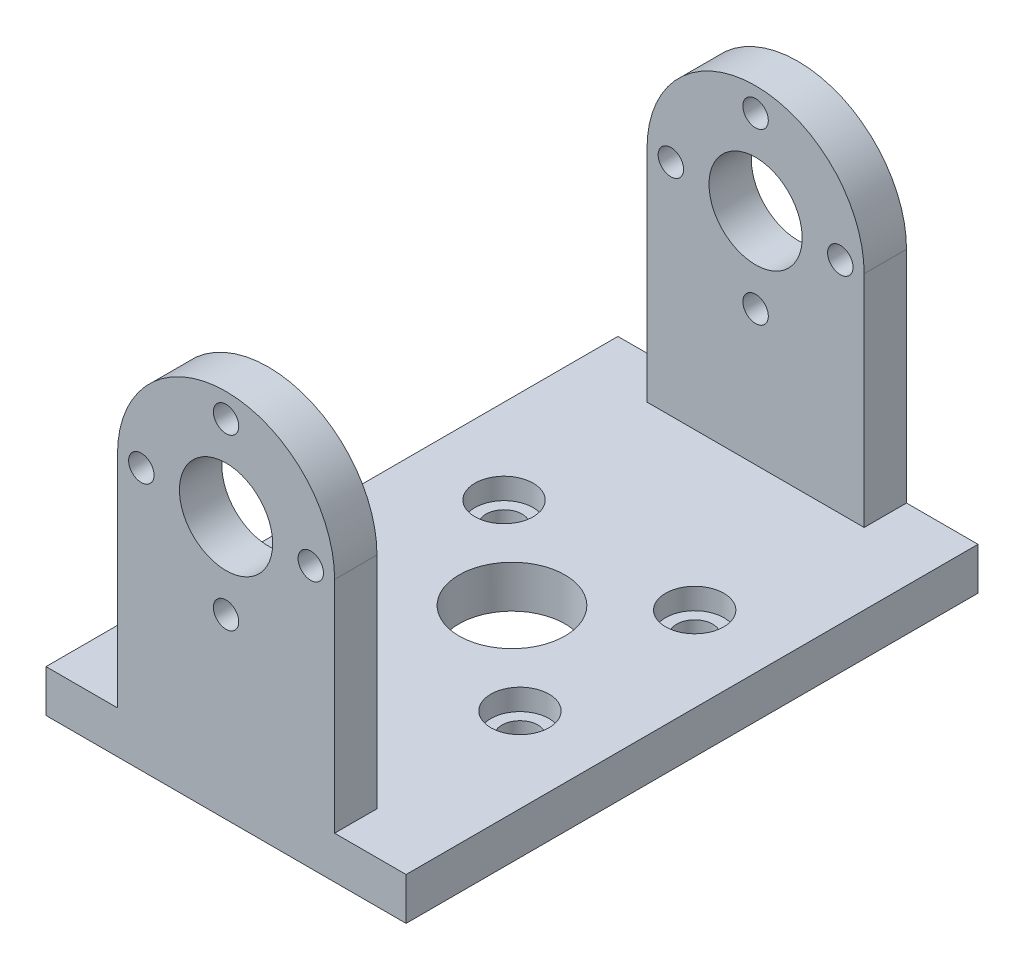
SolidWorks part; units mm, degrees
ref_plane "Front Plane" through (0, 0, 0) normal (0, 0, 1) x (1, 0, 0)
ref_plane "Top Plane" through (0, 0, 0) normal (0, 1, 0) x (1, 0, 0)
ref_plane "Right Plane" through (0, 0, 0) normal (1, 0, 0) x (0, 0, -1)
sketch "Sketch1" plane through (0, 0, 0) normal (0, 0, 1) x (1, 0, 0)
  line L0 (0, 0) -> (0, -68) construction
  line L1 (10.25, 0) -> (10.25, -68)
  line L2 (-10.25, 0) -> (-10.25, -68)
  line L3 (0, 0) -> (0, -68) construction
  line L4 (17, 0) -> (17, -68)
  line L5 (-17, 0) -> (-17, -68)
  line L7 (-10.25, -68) -> (10.25, -68)
  line L8 (-10.25, -68) -> (-10.25, -32.75)
  line L9 (-10.25, -32.75) -> (10.25, -32.75)
  line L10 (10.25, -68) -> (10.25, -32.75)
  line L11 (-17, -32.75) -> (17, -32.75)
  line L12 (-17, -32.75) -> (-17, -28.75)
  line L13 (-17, -28.75) -> (17, -28.75)
  line L14 (17, -32.75) -> (17, -28.75)
  line L15 (-10.25, -68) -> (10.25, -68)
  line L16 (-10.25, -68) -> (-10.25, -79.25)
  line L17 (-10.25, -79.25) -> (10.25, -79.25)
  line L18 (10.25, -68) -> (10.25, -79.25)
  arc A0 (10.25, 0) -> (-10.25, 0) centre (0, 0) ccw
  arc A1 (-10.25, -68) -> (10.25, -68) centre (0, -68) ccw
  arc A2 (17, 0) -> (-17, 0) centre (0, 0) ccw
  arc A3 (-17, -68) -> (17, -68) centre (0, -68) ccw
  circle A4 centre (0, 0) radius 8
  circle A5 centre (0, 8) radius 1.2
  circle A6 centre (8, 0) radius 1.2
  circle A7 centre (0, -8) radius 1.2
  circle A8 centre (-8, 0) radius 1.2
  circle A9 centre (0, -68) radius 10.25
  circle A10 centre (0, 0) radius 4.4
  point P3 (0, -34)
  point P10 (0, -34)
  point P28 (0, 0)
  dimension "D2" = 10.25
  dimension "D3" = 17
  dimension "D4" = 16
  dimension "D5" = 2.4
  dimension "D10" = 8.8
  dimension "D1" = 68
  dimension "D7" = 35.25
  dimension "D8" = 4
  dimension "D9" = 11.25
  dimension "D6" = 4
extrude "Boss-Extrude1" add sketch "Sketch1" along normal blind 4 contours A8 A4 A7 A6 A5 A10 | L1 A0 L2 L13 A8 A4 A5 A6 A7 region at (0, -14.2541, 0) region at (6.5763, 0, 0)
sketch "Sketch3" plane through (0, -28.75, 0) normal (0, -1, 0) x (-1, 0, 0)
  line L21 (-10.25, -4) -> (-10.25, 0) construction
  line L22 (-17, 0) -> (17, 0)
  line L23 (-17, 0) -> (-17, -46)
  line L24 (-17, -46) -> (17, -46)
  line L25 (17, 0) -> (17, -46)
  line L28 (10.25, 0) -> (-10.25, 0) construction
  circle A0 centre (0, -23) radius 5
  circle A1 centre (-9, -14.75) radius 1.7
  circle A2 centre (9, -14.75) radius 1.7
  circle A3 centre (9, -31.25) radius 1.7
  circle A4 centre (-9, -31.25) radius 1.7
  dimension "D3" = 3.4
  dimension "D4" = 8.25
  dimension "D5" = 9
  dimension "D8" = 23
  dimension "D10" = 9
  dimension "D11" = 8.25
  dimension "D13" = 17
  dimension "D1" = 34
  dimension "D2" = 6.75
  dimension "D9" = 46
  dimension "D12" = 0
  dimension "D6" = 2
  dimension "D7" = 2
extrude "Boss-Extrude3" add sketch "Sketch3" against normal blind 4
ref_plane "Plane1" through (0, 0, 23) normal (0, 0, 1) x (1, 0, 0)
mirror "Mirror1" about plane through (0, 0, 23) normal (0, 0, 1) of "Boss-Extrude1"
sketch "Sketch4" plane through (0, -24.75, 0) normal (0, 1, 0) x (1, 0, 0)
  line L1 (-17, -46) -> (17, -46)
  line L2 (-17, -46) -> (-17, 0)
  line L3 (-17, 0) -> (17, 0)
  line L4 (17, -46) -> (17, 0)
  line L5 (-17, -46) -> (17, 0) construction
  line L6 (-17, 0) -> (17, -46) construction
  line L7 (-10.25, 0) -> (10.25, 0)
  line L8 (-10.25, 0) -> (-10.25, -4)
  line L9 (-10.25, -4) -> (10.25, -4)
  line L10 (10.25, 0) -> (10.25, -4)
  line L12 (-10.25, -42) -> (10.25, -42)
  line L13 (-10.25, -42) -> (-10.25, -46)
  line L14 (-10.25, -46) -> (10.25, -46)
  line L15 (10.25, -42) -> (10.25, -46)
  circle A0 centre (-9, -14.75) radius 1.7
  circle A1 centre (-9, -31.25) radius 1.7
  circle A2 centre (0, -23) radius 5
  circle A3 centre (9, -31.25) radius 1.7
  circle A4 centre (9, -14.75) radius 1.7
  point P0 (0, -23)
  circle M5 centre (0, -23) radius 5
  circle M6 centre (9, -14.75) radius 1.7
  circle M7 centre (-9, -14.75) radius 1.7
  circle M8 centre (-9, -31.25) radius 1.7
  circle M9 centre (9, -31.25) radius 1.7
  line M10 (10.25, -42) -> (10.25, -46)
  line M11 (10.25, -46) -> (17, -46)
  line M12 (17, -46) -> (17, 0)
  line M13 (17, 0) -> (10.25, 0)
  line M14 (10.25, 0) -> (10.25, -4)
  line M15 (10.25, -4) -> (-10.25, -4)
  line M16 (-10.25, -4) -> (-10.25, 0)
  line M17 (-10.25, 0) -> (-17, 0)
  line M18 (-17, 0) -> (-17, -46)
  line M19 (-17, -46) -> (-10.25, -46)
  line M20 (-10.25, -46) -> (-10.25, -42)
  line M21 (-10.25, -42) -> (10.25, -42)
extrude "Boss-Extrude4" add sketch "Sketch4" along normal blind 4 contours M21 M10 M11 M12 M13 M14 M15 M16 M17 M18 M19 M20 M6 M8 M9 M7 M5 region at (-16.428, -24.75, 23)
sketch "Sketch5" plane through (-17, 0, 0) normal (-1, 0, 0) x (0, 0, 1)
  line L0 (0, -20.75) -> (0, -28.75) construction
  line L1 (46, -28.75) -> (0, -28.75)
  line L2 (46, -28.75) -> (46, -24.75)
  line L3 (46, -24.75) -> (0, -24.75)
  line L4 (0, -28.75) -> (0, -24.75)
  dimension "D1" = 4
extrude "Cut-Extrude1" cut sketch "Sketch5" against normal through all
sketch "Sketch6" plane through (0, -20.75, 0) normal (0, 1, 0) x (1, 0, 0)
  circle A0 centre (-9, -14.75) radius 2.75
  circle A1 centre (9, -14.75) radius 2.75
  circle A2 centre (9, -31.25) radius 2.75
  circle A3 centre (-9, -31.25) radius 2.75
  dimension "D1" = 5.5
  dimension "D2" = 2
  dimension "D3" = 2
extrude "Cut-Extrude2" cut sketch "Sketch6" against normal blind 2
sketch "Sketch7" plane through (0, -20.75, 0) normal (0, 1, 0) x (1, 0, 0)
  line L1 (-17, 4) -> (17, 4)
  line L2 (-17, 4) -> (-17, -50)
  line L3 (-17, -50) -> (17, -50)
  line L4 (17, 4) -> (17, -50)
  line L6 (-10.25, 0) -> (-17, 0) construction
  line L7 (-17, -46) -> (-10.25, -46) construction
  line L9 (-17, 4) -> (17, 4)
  line L10 (-17, 4) -> (-17, 0)
  line L11 (-17, 0) -> (17, 0)
  line L12 (17, 4) -> (17, 0)
  line L13 (-17, -46) -> (17, -46)
  line L14 (-17, -46) -> (-17, -50)
  line L15 (-17, -50) -> (17, -50)
  line L16 (17, -46) -> (17, -50)
  line M7 (10.25, -46) -> (17, -46)
  line M9 (17, 0) -> (10.25, 0)
  line M13 (-10.25, 0) -> (-17, 0)
  line M15 (-17, -46) -> (-10.25, -46)
  dimension "D1" = 4
  dimension "D2" = 4
extrude "Boss-Extrude5" add sketch "Sketch7" against normal blind 4 contours L11 L4 L1 L2 M13 M9 | L13 L2 L3 L4 M15 M7 region at (0, -20.75, -2) region at (0, -20.75, 48)
ref_plane "Plane2" through (0, 0, 0) normal (0, 0, -1) x (-1, 0, 0)
mirror "Mirror2" about plane through (0, 0, 0) normal (0, 0, -1) of "Boss-Extrude1"
mirror "Mirror3" about plane through (0, 0, 23) normal (0, 0, 1) of "Mirror2"
sketch "Sketch8" plane through (17, 0, 0) normal (1, 0, 0) x (0, 0, -1)
  line L0 (4, -20.75) -> (-4, -20.75) construction
  line L1 (4, -28.75) -> (-50, -28.75)
  line L2 (4, -28.75) -> (4, -24.75)
  line L3 (4, -24.75) -> (-50, -24.75)
  line L4 (-50, -28.75) -> (-50, -24.75)
  line L5 (0, -20.75) -> (-46, -20.75)
  line L6 (0, -20.75) -> (0, 10.25)
  line L7 (0, 10.25) -> (-46, 10.25)
  line L8 (-46, -20.75) -> (-46, 10.25)
  line L9 (-42, 10.25) -> (-50, 10.25) construction
extrude "Cut-Extrude3" cut sketch "Sketch8" against normal through all
